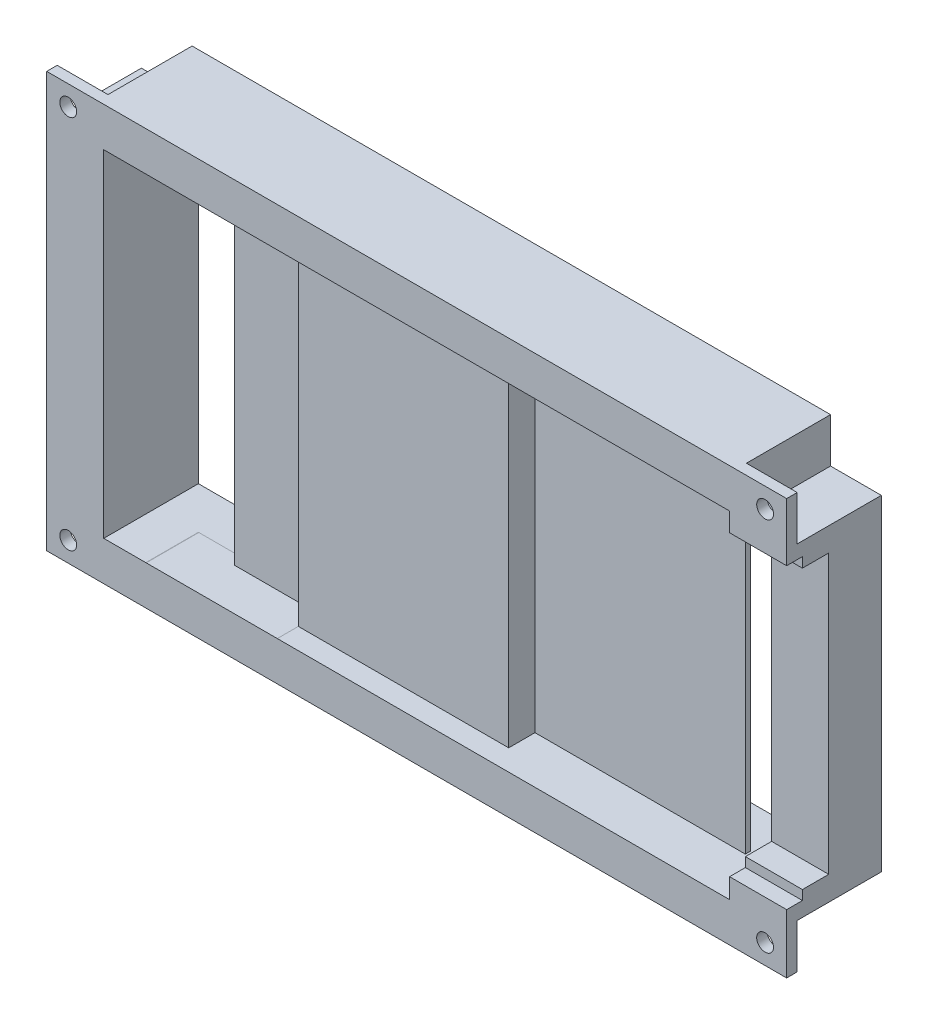
SolidWorks part; units mm, degrees
ref_plane "前视基准面" through (0, 0, 0) normal (0, 0, 1) x (1, 0, 0)
ref_plane "上视基准面" through (0, 0, 0) normal (0, 1, 0) x (1, 0, 0)
ref_plane "右视基准面" through (0, 0, 0) normal (1, 0, 0) x (0, 0, -1)
other "Configuration Table"
sketch "草图1" plane through (0, 0, 0) normal (0, 0, 1) x (1, 0, 0)
  line L1 (-59.5, -32) -> (59.5, -32)
  line L2 (-59.5, -32) -> (-59.5, 32)
  line L3 (-59.5, 32) -> (59.5, 32)
  line L4 (59.5, -32) -> (59.5, 32)
  line L5 (-59.5, -32) -> (59.5, 32) construction
  line L6 (-59.5, 32) -> (59.5, -32) construction
  line L7 (-70.3484, -39.4741) -> (70.3484, -39.4741)
  line L8 (-70.3484, -39.4741) -> (-70.3484, 39.4741)
  line L9 (-70.3484, 39.4741) -> (70.3484, 39.4741)
  line L10 (70.3484, -39.4741) -> (70.3484, 39.4741)
  line L11 (-70.3484, -39.4741) -> (70.3484, 39.4741) construction
  line L12 (-70.3484, 39.4741) -> (70.3484, -39.4741) construction
  point P0 (0, 0)
  point P6 (0, 0)
  dimension "D1" = 119
  dimension "D2" = 64
  dimension "D3" = 140.6968
  dimension "D4" = 78.9483
extrude "凸台-拉伸1" add sketch "草图1" along normal blind 10 and the other way blind 8
sketch "草图2" plane through (0, 0, 0) normal (0, 0, 1) x (1, 0, 0)
  line L0 (59.5, 32) -> (59.5, -32)
  line L1 (59.5, -32) -> (-51.5, -32)
  line L2 (-59.5, -32) -> (59.5, -32) construction
  line L3 (-51.5, -32) -> (-51.5, 32)
  line L4 (59.5, 32) -> (-59.5, 32) construction
  line L5 (-51.5, 32) -> (59.5, 32)
extrude "凸台-拉伸2" add sketch "草图2" along normal blind 10
sketch "草图3" plane through (0, 0, 10) normal (0, 0, 1) x (1, 0, 0)
  line L0 (-51.5, 32) -> (-26.5, 32)
  line L1 (-26.5, 32) -> (-26.5, -31.0616)
  line L2 (-26.5, -31.0616) -> (-51.5, -32)
  line L3 (-51.5, -32) -> (-51.5, 32)
  dimension "D1" = 25
extrude "切除-拉伸1" cut sketch "草图3" against normal blind 8
sketch "草图4" plane through (0, 0, 2) normal (0, 0, 1) x (1, 0, 0)
  line L0 (-51.5, 32) -> (-47.6036, 32)
  line L1 (-26.5, 32) -> (-51.5, 32) construction
  line L2 (-47.6036, 32) -> (-47.6036, -31.8537)
  line L3 (-51.5, -32) -> (-26.5, -31.0616) construction
  line L4 (-47.6036, -31.8537) -> (-51.5, -32)
  line L5 (-51.5, -32) -> (-51.5, 32)
extrude "切除-拉伸2" cut sketch "草图4" against normal through all
sketch "草图5" plane through (0, 0, 10) normal (0, 0, 1) x (1, 0, 0)
  line L0 (59.4984, -32) -> (53.4984, -32)
  line L1 (53.4984, -32) -> (53.4984, 32)
  line L2 (53.4984, 32) -> (59.4984, 32)
  line L3 (59.4984, 32) -> (59.4984, -32)
  line L4 (70.3484, -39.4741) -> (70.3484, 39.4741) construction
  dimension "D1" = 10.85
  dimension "D2" = 6
extrude "切除-拉伸3" cut sketch "草图5" against normal through all
sketch "草图6" plane through (0, 0, 10) normal (0, 0, 1) x (1, 0, 0)
  line L0 (-26.5, 32) -> (53.4984, 32)
  line L1 (53.4984, 32) -> (53.4984, -32)
  line L2 (53.4984, -32) -> (-26.5, -32)
  line L3 (-26.5, -31.0616) -> (-26.5, 32) construction
  line L4 (-26.5, -32) -> (-26.5, 32)
extrude "切除-拉伸4" cut sketch "草图6" against normal blind 4
sketch "草图8" plane through (0, 0, 10) normal (0, 0, 1) x (1, 0, 0)
  line L0 (59.4984, -32) -> (59.4984, 32) construction
  line L1 (70.3484, -39.4741) -> (70.3484, 39.4741) construction
  line L2 (59.4984, 28.4157) -> (70.3484, 28.4157)
  line L3 (59.4984, 28.4157) -> (59.4984, -28.2154)
  line L4 (59.4984, -28.2154) -> (70.3484, -28.2154)
  line L5 (70.3484, 28.4157) -> (70.3484, -28.2154)
extrude "切除-拉伸5" cut sketch "草图8" against normal blind 3
sketch "草图11" plane through (0, 0, 10) normal (0, 0, 1) x (1, 0, 0)
  line L0 (-51.5, -32) -> (-26.5, -31.0616)
  line L1 (-26.5, -31.0616) -> (-26.5, -32)
  line L2 (-26.5, -31.0616) -> (-26.5, -32) construction
  line L3 (-26.5, -32) -> (-51.4295, -31.9974)
  line M11 (-26.5, -32) -> (-26.5, -31.0616)
  line M12 (-26.5, -31.0616) -> (-51.5, -32)
extrude "切除-拉伸8" cut sketch "草图11" against normal blind 8 contours L3 M11 M12 region at (-34.8098, -31.6863, 10)
sketch "草图12" plane through (0, 0, 2) normal (0, 0, 1) x (1, 0, 0)
  line L0 (-51.4295, -31.9974) -> (-47.6036, -31.8537)
  line L1 (-47.6036, -31.8537) -> (-47.6036, -31.9978)
  line L2 (-26.5, -32) -> (-51.4295, -31.9974) construction
  line L3 (-47.6036, -31.9978) -> (-51.4295, -31.9974)
extrude "切除-拉伸9" cut sketch "草图12" against normal through all
sketch "草图14" plane through (0, 0, -8) normal (0, 0, -1) x (-1, 0, 0)
  line L0 (-70.3484, 0) -> (70.3484, 0) construction
  line L1 (70.3484, 39.4741) -> (60.7004, 39.4741)
  line L2 (70.3484, 39.4741) -> (70.3484, 31.0053)
  line L3 (70.3484, 31.0053) -> (60.7004, 31.0053)
  line L4 (60.7004, 39.4741) -> (60.7004, 31.0053)
  line L5 (-70.3484, -39.4741) -> (-70.3484, 39.4741) construction
  line L6 (70.3484, 39.4741) -> (70.3484, -39.4741) construction
  line L7 (0, 39.4741) -> (0, -39.4741) construction
  line L8 (-70.3484, 39.4741) -> (70.3484, 39.4741) construction
  line L9 (70.3484, -39.4741) -> (-70.3484, -39.4741) construction
  line L10 (70.3484, -31.0053) -> (60.7004, -31.0053)
  line L11 (60.7004, -39.4741) -> (60.7004, -31.0053)
  line L12 (70.3484, -39.4741) -> (60.7004, -39.4741)
  line L13 (70.3484, -39.4741) -> (70.3484, -31.0053)
  line L14 (-70.3484, -39.4741) -> (-70.3484, -31.0053)
  line L15 (-70.3484, -39.4741) -> (-60.7004, -39.4741)
  line L16 (-60.7004, -39.4741) -> (-60.7004, -31.0053)
  line L17 (-70.3484, -31.0053) -> (-60.7004, -31.0053)
  line L18 (-70.3484, 31.0053) -> (-60.7004, 31.0053)
  line L19 (-60.7004, 39.4741) -> (-60.7004, 31.0053)
  line L20 (-70.3484, 39.4741) -> (-60.7004, 39.4741)
  line L21 (-70.3484, 39.4741) -> (-70.3484, 31.0053)
extrude "切除-拉伸10" cut sketch "草图14" against normal blind 16
sketch "草图15" plane through (0, 0, 10) normal (0, 0, 1) x (1, 0, 0)
  line L0 (-70.3484, 0) -> (69.7139, 0) construction
  line L1 (-70.3484, 39.4741) -> (-70.3484, -39.4741) construction
  line L2 (0, 39.4741) -> (0, -39.4741) construction
  line L3 (70.3484, 39.4741) -> (-70.3484, 39.4741) construction
  line L4 (-70.3484, -39.4741) -> (70.3484, -39.4741) construction
  circle A0 centre (66.2527, 35.6683) radius 1.6
  circle A1 centre (-66.2527, 35.6683) radius 1.6
  circle A2 centre (-66.2527, -35.6683) radius 1.6
  circle A3 centre (66.2527, -35.6683) radius 1.6
extrude "切除-拉伸11" cut sketch "草图15" against normal blind 5
sketch "草图16" plane through (0, 0, 6) normal (0, 0, 1) x (1, 0, 0)
  line L1 (53.4984, -32) -> (13.4984, -32)
  line L2 (53.4984, -32) -> (53.4984, 32)
  line L3 (53.4984, 32) -> (13.4984, 32)
  line L4 (13.4984, -32) -> (13.4984, 32)
  dimension "D1" = 64
  dimension "D2" = 40
extrude "切除-拉伸12" cut sketch "草图16" against normal blind 5
sketch "草图17" plane through (0, 0, 7) normal (0, 0, 1) x (1, 0, 0)
  line L0 (59.4984, 28.4157) -> (59.4984, -28.2154) construction
  line L1 (59.4984, 26.5138) -> (70.3484, 26.5138)
  line L2 (59.4984, 26.5138) -> (59.4984, -26.4048)
  line L3 (59.4984, -26.4048) -> (70.3484, -26.4048)
  line L4 (70.3484, 26.5138) -> (70.3484, -26.4048)
  line L5 (70.3484, -28.2154) -> (70.3484, 28.4157) construction
extrude "切除-拉伸13" cut sketch "草图17" against normal blind 5
sketch "草图19" plane through (0, 0, 2) normal (0, 0, 1) x (1, 0, 0)
  line L0 (-47.6036, 32) -> (-42.6036, 32)
  line L1 (59.4984, 32) -> (-59.5, 32) construction
  line L2 (-42.6036, 32) -> (-42.6036, -31.9983)
  line L3 (-26.5, -32) -> (-47.6036, -31.9978) construction
  line L4 (-42.6036, -31.9983) -> (-47.6036, -31.9978)
  line L5 (-47.6036, -31.9978) -> (-47.6036, 32)
  dimension "D1" = 5
extrude "切除-拉伸21" cut sketch "草图19" against normal blind 10
